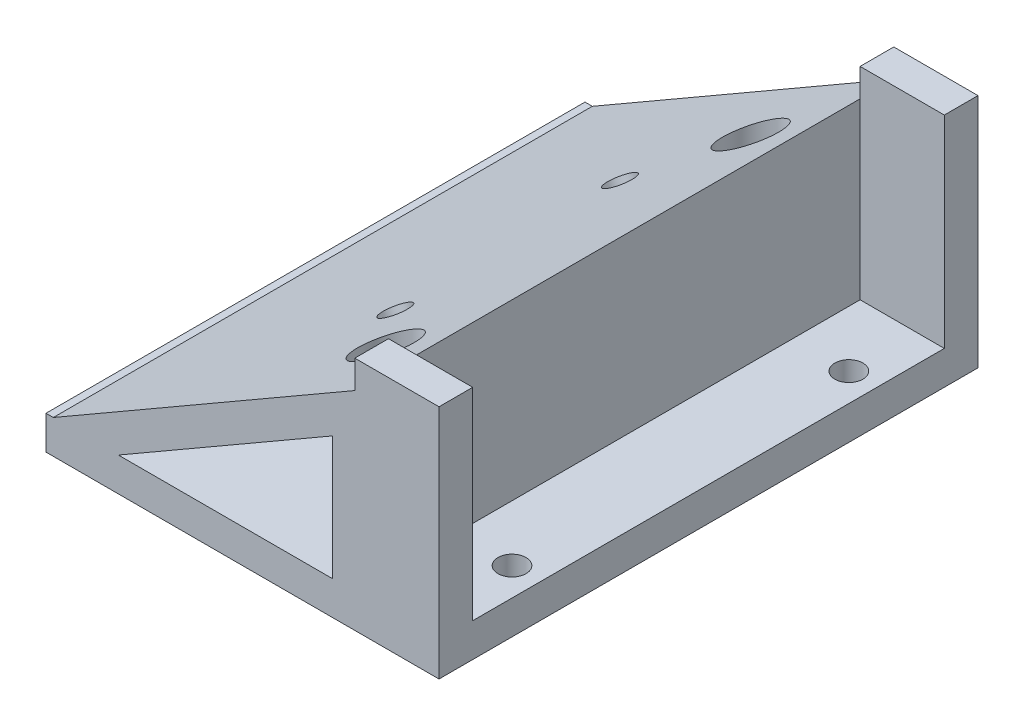
SolidWorks part; units mm, degrees
ref_plane "Front Plane" through (0, 0, 0) normal (0, 0, 1) x (1, 0, 0)
ref_plane "Top Plane" through (0, 0, 0) normal (0, 1, 0) x (1, 0, 0)
ref_plane "Right Plane" through (0, 0, 0) normal (1, 0, 0) x (0, 0, -1)
sketch "Sketch1" plane through (0, 0, 0) normal (0, 1, 0) x (1, 0, 0)
  line L1 (-70.1234, 25.0109) -> (-105.1234, 25.0109)
  line L2 (-70.1234, 25.0109) -> (-70.1234, 73.0109)
  line L3 (-70.1234, 73.0109) -> (-105.1234, 73.0109)
  line L4 (-105.1234, 25.0109) -> (-105.1234, 73.0109)
  dimension "D1" = 48
  dimension "D2" = 35
extrude "Boss-Extrude1" add sketch "Sketch1" along normal blind 3
sketch "Sketch2" plane through (0, 3, 0) normal (0, 1, 0) x (1, 0, 0)
  line L0 (-70.1234, 73.0109) -> (-105.1234, 73.0109) construction
  line L1 (-70.1234, 25.0109) -> (-70.1234, 73.0109) construction
  line L2 (-105.1234, 25.0109) -> (-70.1234, 25.0109) construction
  circle A1 centre (-82.6234, 65.264) radius 1.5
  circle A2 centre (-82.6234, 32.764) radius 1.5
  circle A3 centre (-72.6234, 34.0109) radius 1.25
  circle A4 centre (-72.6234, 64.0109) radius 1.25
  dimension "D8" = 3
  dimension "D9" = 3
  dimension "D10" = 2.5
  dimension "D11" = 2.5
  dimension "D1" = 30
  dimension "D2" = 32.5
  dimension "D3" = 10
  dimension "D4" = 10
  dimension "D5" = 9
  dimension "D6" = 2.5
  dimension "D7" = 2.5
  dimension "D12" = 7.7531
extrude "Cut-Extrude1" cut sketch "Sketch2" against normal through all
sketch "Sketch4" plane through (0, 0, -25.0109) normal (0, 0, 1) x (1, 0, 0)
  line L0 (-77.6234, 3) -> (-104.4702, 3)
  line L2 (-104.4702, 3) -> (-77.6234, 18.5)
  line L3 (-77.6234, 18.5) -> (-77.6234, 3)
  line L7 (-105.1234, 3) -> (-70.1234, 3) construction
  line L8 (-70.1234, 3) -> (-70.1234, 0) construction
  dimension "D1" = 31
  dimension "D2" = 30
  dimension "D3" = 60
  dimension "D4" = 7.5
extrude "Boss-Extrude2" add sketch "Sketch4" against normal blind 48 contours L0 L2 L3
sketch "Sketch6" plane through (0, 0, -25.0109) normal (0, 0, 1) x (1, 0, 0)
  line L0 (-98.676, 3) -> (-79.6234, 3)
  line L2 (-98.676, 3) -> (-79.6234, 14)
  line L3 (-79.6234, 14) -> (-79.6234, 3)
  line L10 (-77.6234, 3) -> (-70.1234, 3) construction
  dimension "D1" = 30
  dimension "D2" = 60
  dimension "D3" = 2
  dimension "D4" = 22
extrude "Cut-Extrude5" cut sketch "Sketch6" against normal through all contours L0 L3 L2
sketch "Sketch8" plane through (0, 3, 0) normal (0, 1, 0) x (1, 0, 0)
  circle A0 centre (-82.6234, 32.764) radius 2.5
  circle A1 centre (-82.6234, 32.764) radius 1.5 construction
  circle A2 centre (-82.6234, 65.264) radius 2.5
  circle A3 centre (-82.6234, 65.264) radius 1.5 construction
  dimension "D1" = 5
  dimension "D2" = 5
extrude "Cut-Extrude6" cut sketch "Sketch8" against normal blind 1 and the other way through all
sketch "Sketch9" plane through (-27.4166, 47.4869, 0) normal (-0.5, 0.866, 0) x (0.866, 0.5, 0)
  line L0 (-88.9739, 73.0109) -> (-57.9739, 73.0109) construction
  line L1 (-57.9739, 73.0109) -> (-57.9739, 25.0109) construction
  circle A0 centre (-69.9739, 59.0109) radius 1.25
  circle A1 centre (-69.9739, 39.0109) radius 1.25
  dimension "D1" = 2.5
  dimension "D2" = 2.5
  dimension "D3" = 20
  dimension "D4" = 14
  dimension "D5" = 12
  dimension "D6" = 12
extrude "Cut-Extrude7" cut sketch "Sketch9" against normal up to next
sketch "Sketch10" plane through (-25.968, 44.978, 0) normal (0.5, -0.866, 0) x (-0.866, -0.5, 0)
  circle A0 centre (69.9739, 59.0109) radius 2.5
  circle A1 centre (69.9739, 39.0109) radius 2.5
  circle A3 centre (69.9739, 39.0109) radius 1.25 construction
  circle A4 centre (69.9739, 59.0109) radius 1.25 construction
  dimension "D1" = 5
  dimension "D2" = 5
extrude "Cut-Extrude8" cut sketch "Sketch10" against normal blind 0.5 and the other way up to next
sketch "Sketch11" plane through (0, 3, 0) normal (0, 1, 0) x (1, 0, 0)
  line L0 (-77.6234, 25.0109) -> (-70.1234, 25.0109) construction
  line L1 (-70.1234, 25.0109) -> (-77.6234, 25.0109)
  line L2 (-70.1234, 25.0109) -> (-70.1234, 28.0109)
  line L3 (-70.1234, 28.0109) -> (-77.6234, 28.0109)
  line L4 (-77.6234, 25.0109) -> (-77.6234, 28.0109)
  line L5 (-70.1234, 70.0109) -> (-77.6234, 70.0109)
  line L6 (-70.1234, 70.0109) -> (-70.1234, 73.0109)
  line L7 (-70.1234, 73.0109) -> (-77.6234, 73.0109)
  line L8 (-77.6234, 70.0109) -> (-77.6234, 73.0109)
  line L9 (-70.1234, 73.0109) -> (-77.6234, 73.0109) construction
  line L10 (-70.1234, 25.0109) -> (-70.1234, 73.0109) construction
  line L11 (-77.6234, 73.0109) -> (-77.6234, 25.0109) construction
  dimension "D1" = 3
  dimension "D2" = 3
  dimension "D3" = 0
  dimension "D4" = 0
  dimension "D5" = 0
  dimension "D6" = 0
  dimension "D7" = 0
  dimension "D8" = 0
extrude "Boss-Extrude3" add sketch "Sketch11" along normal blind 18
